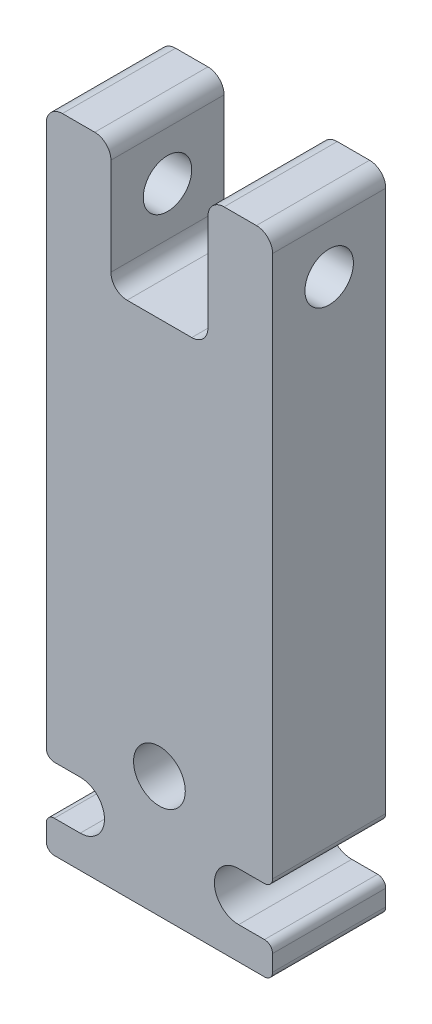
SolidWorks part; units mm, degrees
ref_plane "Alzado" through (0, 0, 0) normal (0, 0, 1) x (1, 0, 0)
ref_plane "Planta" through (0, 0, 0) normal (0, 1, 0) x (1, 0, 0)
ref_plane "Vista lateral" through (0, 0, 0) normal (1, 0, 0) x (0, 0, -1)
sketch "Croquis1" plane through (0, 0, 0) normal (0, 0, 1) x (1, 0, 0)
  line L0 (3, 20) -> (7, 20)
  line L1 (-7, 20) -> (-3, 20)
  line L2 (-7, 20) -> (-7, -15)
  line L3 (-7, -20) -> (7, -20)
  line L4 (7, 20) -> (7, -15)
  line L5 (-7, 20) -> (7, -20) construction
  line L6 (-7, -20) -> (7, 20) construction
  line L7 (-3, 20) -> (3, 20) construction
  line L8 (-3, 20) -> (-3, 12)
  line L9 (-3, 12) -> (3, 12)
  line L10 (3, 20) -> (3, 12)
  line L11 (0, 0) -> (0, -20) construction
  line L12 (4.9, -15) -> (7, -15)
  line L13 (4.9, -18) -> (7, -18)
  line L14 (-4.9, -15) -> (-7, -15)
  line L15 (-4.9, -18) -> (-7, -18)
  line L16 (-7, -18) -> (-7, -20)
  line L17 (7, -18) -> (7, -20)
  arc A1 (4.9, -15) -> (4.9, -18) centre (4.9, -16.5) ccw
  arc A2 (-4.9, -18) -> (-4.9, -15) centre (-4.9, -16.5) ccw
  circle A3 centre (0, -12.5) radius 1.6
  point P0 (0, 0)
  point P10 (0, 12)
  point P14 (-3.4, -16.5)
  point P16 (3.4, -16.5)
  point P17 (6.4, -16.5)
  point P19 (4.9, -18)
  point P29 (0, -14.1)
  dimension "D5" = 4
  dimension "D7" = 3
  dimension "D6" = 3.2
  dimension "D1" = 14
  dimension "D2" = 40
  dimension "D3" = 6
  dimension "D4" = 8
  dimension "D8" = 9.8
  dimension "D9" = 2
extrude "Saliente-Extruir1" add sketch "Croquis1" along normal mid plane 7
sketch "Croquis2" plane through (0, 0, 0) normal (1, 0, 0) x (0, 0, -1)
  line L0 (-3.5, 20) -> (3.5, 20) construction
  circle A0 centre (0, 16) radius 1.5
  dimension "D1" = 3
  dimension "D2" = 4
extrude "Cortar-Extruir1" cut sketch "Croquis2" against normal through all both and the other way through all
fillet "Redondeo1" radius 1 6 edges at (-7, 20, 0) (-3, 20, 0) (-3, 12, 0) (3, 12, 0) (3, 20, 0) (7, 20, 0)
fillet "Redondeo2" radius 0.5 6 edges at (7, -20, 0) (-7, -20, 0) (7, -18, 0) (7, -15, 0) (-7, -18, 0) (-7, -15, 0)
